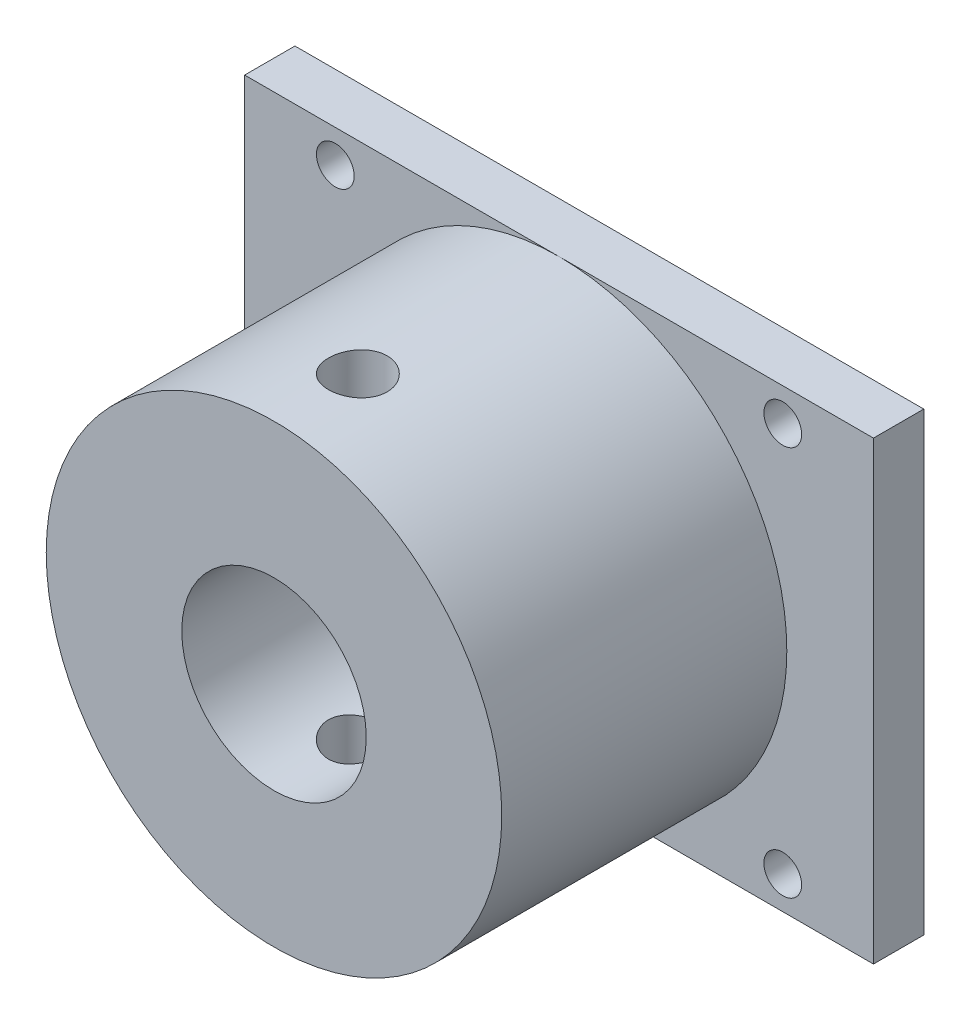
SolidWorks part; units mm, degrees
ref_plane "Front Plane" through (0, 0, 0) normal (0, 0, 1) x (1, 0, 0)
ref_plane "Top Plane" through (0, 0, 0) normal (0, 1, 0) x (1, 0, 0)
ref_plane "Right Plane" through (0, 0, 0) normal (1, 0, 0) x (0, 0, -1)
sketch "Sketch1" plane through (0, 0, 0) normal (0, 0, 1) x (1, 0, 0)
  line L1 (37.5, -27.165) -> (-37.5, -27.165)
  line L2 (37.5, -27.165) -> (37.5, 27.165)
  line L3 (37.5, 27.165) -> (-37.5, 27.165)
  line L4 (-37.5, -27.165) -> (-37.5, 27.165)
  line L5 (37.5, -27.165) -> (-37.5, 27.165) construction
  line L6 (37.5, 27.165) -> (-37.5, -27.165) construction
  point P0 (0, 0)
  dimension "D1" = 54.33
  dimension "D2" = 75
extrude "Boss-Extrude1" add sketch "Sketch1" along normal blind 45
sketch "Sketch2" plane through (0, 0, 45) normal (0, 0, 1) x (1, 0, 0)
  line L0 (0, 0) -> (0, -50000) construction
  line L1 (0, 0) -> (50000, 0) construction
  circle A0 centre (26.685, 23.265) radius 2
  circle A1 centre (-26.685, 23.265) radius 2
  circle A2 centre (-26.685, -23.265) radius 2
  circle A3 centre (26.685, -23.265) radius 2
  point P5 (26.685, 23.265)
  point P7 (-26.685, 23.265)
  point P9 (-26.685, -23.265)
  point P11 (26.685, -23.265)
  dimension "D1" = 4
  dimension "D2" = 53.37
  dimension "D3" = 46.53
hole_wizard "CBORE for M4 SHCS1" positions "Sketch2" profile "Sketch3" counterbore size "M4" standard "ANSI Metric" end condition through all
sketch "Sketch3" plane through (26.685, -23.265, 45) normal (1, 0, 0) x (0, -1, 0)
  line L0 (0, 0) -> (0, 45)
  line L1 (0, 45) -> (2.25, 45)
  line L3 (2.25, 45) -> (2.25, 4)
  line L4 (2.25, 4) -> (4, 4)
  line L5 (4, 4) -> (4, 0)
  line L7 (4, 0) -> (0, 0)
  line L11 (0, -6.35) -> (0, 107.95) construction
  dimension "Thru Hole Dia." = 4.5
  dimension "Thru Hole Depth" = 45
  dimension "C'Bore Dia." = 8
  dimension "C'Bore Depth" = 4
sketch "Sketch4" plane through (0, -27.165, 0) normal (0, -1, 0) x (1, 0, 0)
  line L0 (-37.5, 45) -> (-37.5, 0) construction
  line L1 (37.5, 0) -> (-37.5, 0)
  line L2 (37.5, 0) -> (37.5, 40)
  line L3 (37.5, 40) -> (-37.5, 40)
  line L4 (-37.5, 0) -> (-37.5, 40)
  dimension "D1" = 40
extrude "Cut-Extrude1" cut sketch "Sketch4" against normal through all flip side to cut
sketch "Sketch5" plane through (0, 0, 40) normal (0, 0, 1) x (1, 0, 0)
  circle A0 centre (0, 0) radius 11
  circle A1 centre (0, 0) radius 9
  circle A2 centre (0, 0) radius 8.5
  dimension "D1" = 17
  dimension "D2" = 18
  dimension "D3" = 22
extrude "Cut-Extrude2" cut sketch "Sketch5" against normal blind 30 contours A2
extrude "Cut-Extrude3" cut sketch "Sketch5<3>" against normal blind 20 contours A1
sketch "Sketch5<3>" plane through (0, 0, 40) normal (0, 0, 1) x (1, 0, 0) same geometry as "Sketch5"
extrude "Cut-Extrude4" cut sketch "Sketch5<4>" against normal blind 17 contours A0
sketch "Sketch5<4>" plane through (0, 0, 40) normal (0, 0, 1) x (1, 0, 0) same geometry as "Sketch5"
sketch "Sketch6" plane through (0, 27.165, 0) normal (0, 1, 0) x (1, 0, 0)
  line L0 (0, 0) -> (0, -50000) construction
  line L1 (37.5, 0) -> (-37.5, 0) construction
  circle A0 centre (0, -30) radius 3.5
  point P4 (0, 0)
  dimension "D1" = 7
  dimension "D2" = 30
extrude "Cut-Extrude5" cut sketch "Sketch6" against normal through all
sketch "Sketch29" plane through (0, 0, 40) normal (0, 0, 1) x (1, 0, 0)
  line L5 (37.5, 27.165) -> (-37.5, 27.165) construction
  circle A0 centre (0, 0) radius 27.165
extrude "Cut-Extrude6" cut sketch "Sketch29" against normal blind 34 flip side to cut
sketch "Sketch30" plane through (0, 0, 0) normal (0, 0, -1) x (-1, 0, 0)
  line L0 (0, 0) -> (0, -50000) construction
  line L1 (0, 0) -> (50000, 0) construction
  circle A0 centre (-13.555, 11.3) radius 4.5
  circle A1 centre (13.555, 11.3) radius 4.5
  circle A2 centre (13.555, -11.3) radius 4.5
  circle A3 centre (-13.555, -11.3) radius 4.5
  dimension "D3" = 9
  dimension "D1" = 27.11
  dimension "D2" = 22.6
extrude "Cut-Extrude7" cut sketch "Sketch30" against normal blind 5
